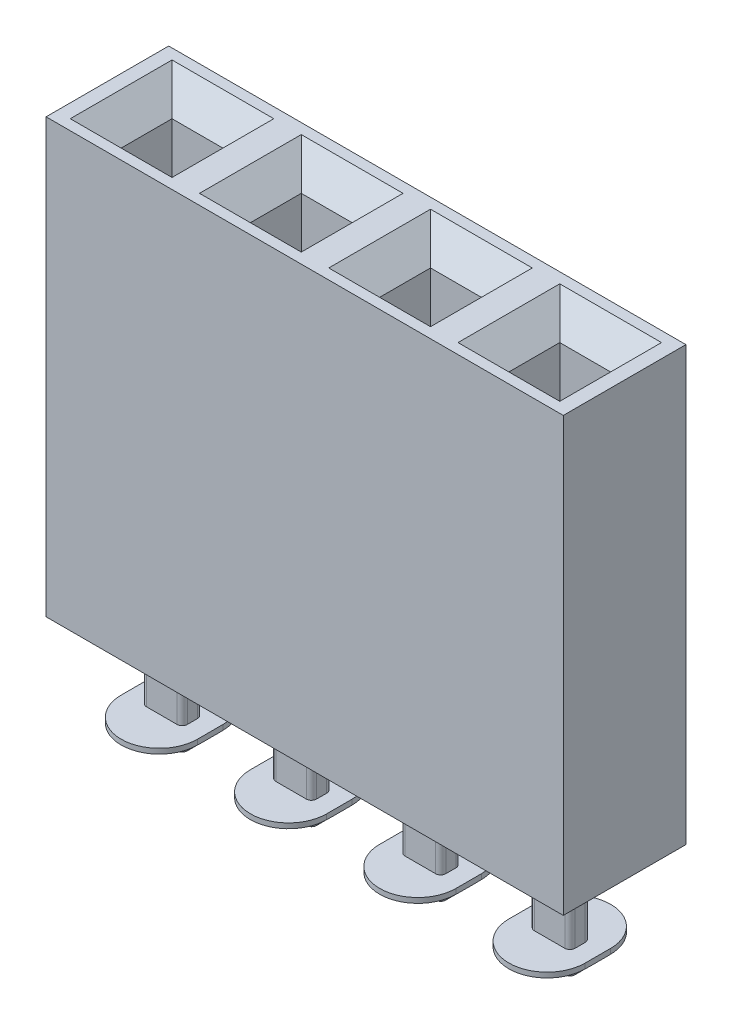
SolidWorks part; units mm, degrees
material "PA Type 6"
ref_plane "Front Plane" through (0, 0, 0) normal (0, 0, 1) x (1, 0, 0)
ref_plane "Top Plane" through (0, 0, 0) normal (0, 1, 0) x (1, 0, 0)
ref_plane "Right Plane" through (0, 0, 0) normal (1, 0, 0) x (0, 0, -1)
ref_plane "Plane1" through (0, -1.65, 0) normal (0, 1, 0) x (1, 0, 0)
sketch "Sketch2" plane through (0, 0, 0) normal (0, 1, 0) x (1, 0, 0)
  line L0 (0, -55) -> (0, 55) construction
  line L1 (-1.27, 1.205) -> (13.97, 1.205)
  line L2 (-1.27, 1.205) -> (-1.27, -1.205)
  line L3 (-1.27, -1.205) -> (13.97, -1.205)
  line L4 (13.97, 1.205) -> (13.97, -1.205)
  line L5 (-55, 0) -> (55, 0) construction
  dimension "D1" = 15.24
  dimension "D2" = 1.27
  dimension "D3" = 2.41
  dimension "D4" = 1.205
extrude "Boss-Extrude1" add sketch "Sketch2" along normal blind 8.51
sketch "Sketch5" plane through (0, 8.51, 0) normal (0, 1, 0) x (1, 0, 0)
  line L0 (-55, 0) -> (55, 0) construction
  line L1 (0.5, 0.5) -> (-0.5, 0.5)
  line L2 (0.5, 0.5) -> (0.5, -0.5)
  line L3 (0.5, -0.5) -> (-0.5, -0.5)
  line L4 (-0.5, 0.5) -> (-0.5, -0.5)
  line L5 (0, -55) -> (0, 55) construction
  dimension "D1" = 0.5
  dimension "D2" = 1
  dimension "D3" = 0.5
extrude "Cut-Extrude1" cut sketch "Sketch5" against normal blind 5
chamfer "Chamfer1" distance 0.5 angle 45 4 edges at (-0.5, 8.51, 0) (0, 8.51, 0.5) (0.5, 8.51, 0) (0, 8.51, -0.5)
pattern_linear "LPattern3" count 6 spacing 2.54 along (1, 0, 0) of "Chamfer1", "Cut-Extrude1"
sketch "Sketch8" plane through (0, 0, 0) normal (0, 1, 0) x (1, 0, 0)
  line L0 (0, -1.3255) -> (0, 1.3255) construction
  line L1 (-0.3, -0.2) -> (0.3, -0.2)
  line L2 (-0.4, -0.1) -> (-0.4, 0.1)
  line L3 (-0.3, 0.2) -> (0.3, 0.2)
  line L4 (0.4, -0.1) -> (0.4, 0.1)
  line L5 (-4.6805, 0) -> (4.6805, 0) construction
  arc A0 (-0.3, -0.2) -> (-0.4, -0.1) centre (-0.3, -0.1) cw
  arc A1 (0.3, -0.2) -> (0.4, -0.1) centre (0.3, -0.1) ccw
  arc A2 (0.3, 0.2) -> (0.4, 0.1) centre (0.3, 0.1) cw
  arc A3 (-0.4, 0.1) -> (-0.3, 0.2) centre (-0.3, 0.1) cw
  point P10 (-0.4, -0.2)
  point P13 (0.4, -0.2)
  point P16 (0.4, 0.2)
  dimension "D5" = 0.1
  dimension "D1" = 0.4
  dimension "D2" = 0.8
  dimension "D3" = 0.4
  dimension "D4" = 0.2
extrude "Boss-Extrude2" add sketch "Sketch8" against normal blind 2
sketch "Sketch10" plane through (0, -1.65, 0) normal (0, 1, 0) x (1, 0, 0)
  line L0 (0, -0.25) -> (0, 0.25) construction
  line L1 (0, -1.3255) -> (0, 1.3255) construction
  line L2 (-0.75, -0.25) -> (-0.75, 0.25)
  line L3 (0.75, -0.25) -> (0.75, 0.25)
  line L4 (-5.7805, 0) -> (5.7805, 0) construction
  arc A0 (-0.75, -0.25) -> (0.75, -0.25) centre (0, -0.25) ccw
  arc A1 (0.75, 0.25) -> (-0.75, 0.25) centre (0, 0.25) ccw
  point P5 (0, 0)
  dimension "D1" = 1.5
  dimension "D2" = 0.5
extrude "Boss-Extrude3" add sketch "Sketch10" along normal blind 0.1
fillet "Fillet2" radius 0.4 6 edges at (-0.3707, -1.65, -0.1707) (-0.3707, -1.65, 0.1707) (0, -1.65, 0.2) (0.3707, -1.65, 0.1707) (0.3707, -1.65, -0.1707) (0, -1.65, -0.2)
pattern_linear "LPattern1" count 6 spacing 2.54 along (1, 0, 0) of "Boss-Extrude2", "Fillet2", "Boss-Extrude3"
ref_axis "Axis1" through (0, -2.5255, 0) along (0, 1, 0)
sketch "Croquis1" plane through (0, 0, 0) normal (0, 0, 1) x (1, 0, 0)
  line L0 (8.8943, 0) -> (8.8943, 8.51)
  line L1 (-1.27, 0) -> (13.97, 0) construction
  line L2 (-1.27, 8.51) -> (13.97, 8.51) construction
  line L3 (8.8943, 8.51) -> (13.97, 8.51)
  line L4 (13.97, 8.51) -> (13.97, 0)
  line L5 (13.97, 0) -> (13.97, -2.7721)
  line L6 (13.97, -2.7721) -> (8.8943, -2.7721)
  line L7 (8.8943, -2.7721) -> (8.8943, 0)
extrude "Cortar-Extruir1" cut sketch "Croquis1" against normal mid plane 10
equation "\"D1@Sketch2\"=2.54 *6"
